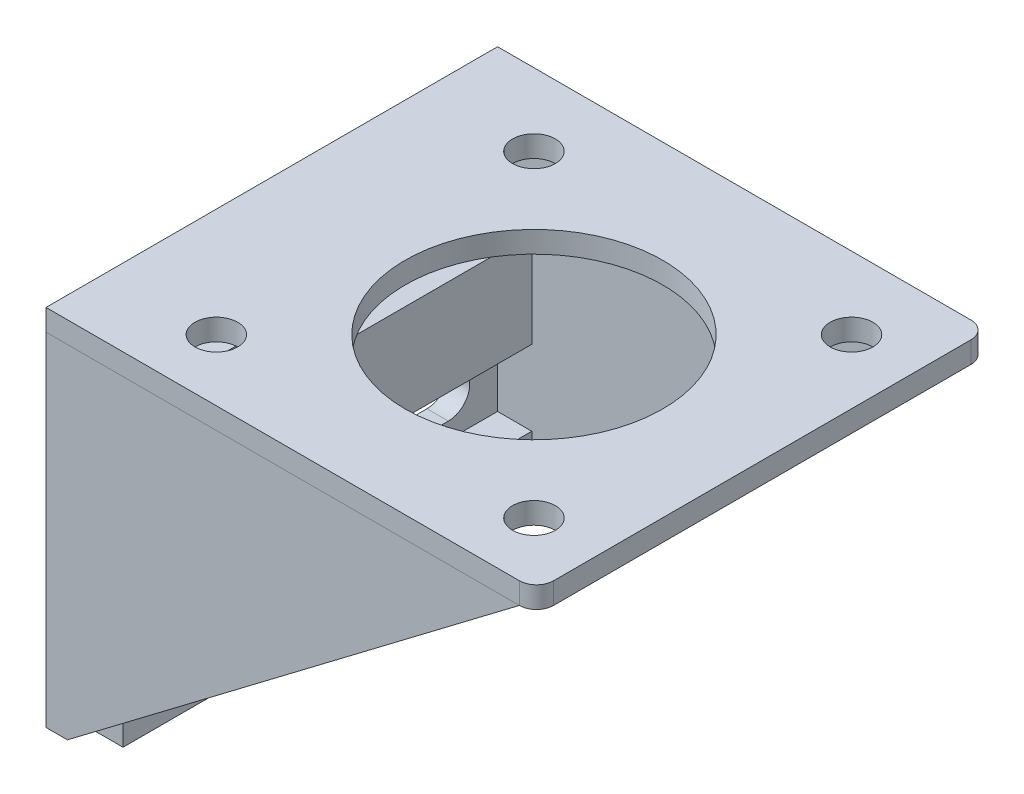
SolidWorks part; units mm, degrees
ref_plane "Front Plane" through (0, 0, 0) normal (0, 0, 1) x (1, 0, 0)
ref_plane "Top Plane" through (0, 0, 0) normal (0, 1, 0) x (1, 0, 0)
ref_plane "Right Plane" through (0, 0, 0) normal (1, 0, 0) x (0, 0, -1)
sketch "Sketch1" plane through (0, 0, 0) normal (0, 1, 0) x (1, 0, 0)
  line L0 (-26.2255, 26.2255) -> (-26.2255, -26.2255) construction
  line L1 (-26.2255, -26.2255) -> (26.2255, -26.2255) construction
  line L2 (26.2255, -26.2255) -> (26.2255, 26.2255) construction
  line L3 (26.2255, 26.2255) -> (-26.2255, 26.2255) construction
  line L4 (-26.2255, 26.2255) -> (26.2255, -26.2255) construction
  line L5 (-39.6875, 34.29) -> (33.0835, 34.29)
  line L6 (33.0835, 34.29) -> (33.0835, -32.7025)
  line L7 (33.0835, -32.7025) -> (-39.6875, -32.7025)
  line L8 (-39.6875, -32.7025) -> (-39.6875, 34.29)
  line L9 (-23.5585, 23.5585) -> (23.5585, 23.5585) construction
  line L10 (23.5585, 23.5585) -> (23.5585, -23.5585) construction
  line L11 (23.5585, -23.5585) -> (-23.5585, -23.5585) construction
  line L12 (-23.5585, -23.5585) -> (-23.5585, 23.5585) construction
  line L13 (26.7335, 27.5945) -> (26.7335, 19.7469) construction
  circle A0 centre (0, 0) radius 19.1135
  circle A1 centre (-23.5585, 23.5585) radius 2.667 construction
  circle A2 centre (23.5585, 23.5585) radius 2.667 construction
  circle A3 centre (-23.5585, -23.5585) radius 2.667 construction
  circle A4 centre (23.5585, -23.5585) radius 2.667 construction
  circle A5 centre (-23.5585, 23.5585) radius 3.175
  circle A6 centre (23.5585, 23.5585) radius 3.175
  circle A7 centre (23.5585, -23.5585) radius 3.175
  circle A8 centre (-23.5585, -23.5585) radius 3.175
  point P13 (0, 0)
  dimension "D1" = 38.227
  dimension "D2" = 5.334
  dimension "D8" = 6.35
  dimension "D3" = 52.451
  dimension "D5" = 34.29
  dimension "D6" = 32.7025
  dimension "D7" = 39.6875
  dimension "D4" = 6.35
extrude "Boss-Extrude1" add sketch "Sketch1" along normal blind 3.175
fillet "Fillet1" radius 2.54 2 edges at (33.0835, 1.5875, 32.7025) (33.0835, 1.5875, -34.29)
sketch "Sketch2" plane through (-39.6875, 0, 0) normal (-1, 0, 0) x (0, 0, 1)
  line L0 (-34.29, 0) -> (-34.29, -50.8)
  line L2 (32.7025, -50.8) -> (32.7025, 0)
  line L3 (-34.29, 0) -> (32.7025, 0)
  line L4 (32.7025, -50.8) -> (-34.29, -50.8)
  line L5 (-0.7938, 0) -> (-0.7938, -50.8) construction
  point P6 (-0.7938, -50.8)
  dimension "D1" = 50.8
extrude "Boss-Extrude2" add sketch "Sketch2" against normal blind 3.175
ref_plane "Plane1" through (-36.5125, 0, -34.29) normal (0, -1, 0) x (-1, 0, 0)
sketch "Sketch7" plane through (0, 0, 32.7025) normal (0, 0, 1) x (1, 0, 0)
  line L0 (-36.5125, -50.8) -> (30.5435, 0)
  line L1 (30.5435, 0) -> (-36.5125, 0)
  line L2 (-91.5125, 0) -> (18.4875, 0) construction
  line L3 (-36.5125, 0) -> (-36.5125, -50.8)
extrude "Boss-Extrude5" add sketch "Sketch7" against normal blind 3.175
sketch "Sketch8" plane through (0, 0, -34.29) normal (0, 0, -1) x (-1, 0, 0)
  line L0 (-30.5435, 0) -> (36.5125, 0)
  line L1 (36.5125, 0) -> (36.5125, -50.8)
  line L2 (36.5125, -50.8) -> (-30.5435, 0)
extrude "Boss-Extrude6" add sketch "Sketch8" against normal blind 3.175
sketch "Sketch9" plane through (-36.5125, 0, 0) normal (1, 0, 0) x (0, 0, -1)
  line L0 (-12.3825, -9.525) -> (23.8125, -9.525) construction
  line L1 (23.8125, -9.525) -> (23.8125, -34.925) construction
  line L2 (23.8125, -34.925) -> (-12.3825, -34.925) construction
  line L3 (-12.3825, -34.925) -> (-12.3825, -9.525) construction
  line L6 (-2.2225, -6.35) -> (-12.3825, -6.35)
  line L7 (-2.2225, -12.7) -> (-12.3825, -12.7)
  line L8 (-2.2225, -31.75) -> (-12.3825, -31.75)
  line L9 (-2.2225, -38.1) -> (-12.3825, -38.1)
  line L10 (23.8125, -38.1) -> (13.6525, -38.1)
  line L11 (23.8125, -31.75) -> (13.6525, -31.75)
  line L12 (23.8125, -6.35) -> (13.6525, -6.35)
  line L13 (23.8125, -12.7) -> (13.6525, -12.7)
  line L14 (-30.1625, 3.175) -> (31.75, 3.175) construction
  circle A0 centre (23.8125, -9.525) radius 3.175
  circle A1 centre (-12.3825, -9.525) radius 3.175
  circle A2 centre (23.8125, -34.925) radius 3.175
  circle A3 centre (-12.3825, -34.925) radius 3.175
  circle A4 centre (-2.2225, -9.525) radius 3.175
  circle A5 centre (13.6525, -9.525) radius 3.175
  circle A6 centre (13.6525, -34.925) radius 3.175
  circle A7 centre (-2.2225, -34.925) radius 3.175
  dimension "D1" = 6.35
  dimension "D2" = 12.3825
  dimension "D3" = 25.4
  dimension "D4" = 10.16
  dimension "D5" = 10.16
  dimension "D6" = 12.7
  dimension "D7" = 26.035
extrude "Cut-Extrude1" cut sketch "Sketch9" against normal blind 3.175 contours A4 L6 A1 L7 | A4 | A1 | A5 L13 A0 L12 | A5 | A0 | A2 | A6 L10 A2 L11 | A6 | A7 | A7 L8 A3 L9 | A3 region at (-36.5125, -9.525, 7.3025) region at (-36.5125, -9.525, 2.2225) region at (-36.5125, -9.525, 12.3825) region at (-36.5125, -34.925, 7.3025) region at (-36.5125, -34.925, 2.2225) region at (-36.5125, -34.925, 12.3825) region at (-36.5125, -34.925, -18.7325) region at (-36.5125, -34.925, -23.8125) region at (-36.5125, -34.925, -13.6525) region at (-36.5125, -9.525, -18.7325) region at (-36.5125, -9.525, -23.8125) region at (-36.5125, -9.525, -13.6525)
sketch "Sketch10" plane through (-36.5125, 0, 0) normal (1, 0, 0) x (0, 0, -1)
  line L0 (-29.5275, 0) -> (31.115, 0)
  line L1 (31.115, 0) -> (31.115, -3.937)
  line L2 (31.115, 0) -> (31.115, -50.8) construction
  line L3 (31.115, -3.937) -> (-29.5275, -3.937)
  line L4 (-29.5275, 0) -> (-29.5275, -50.8) construction
  line L5 (-29.5275, -3.937) -> (-29.5275, 0)
  line L6 (31.115, -15.113) -> (-29.5275, -15.113)
  line L7 (31.115, -50.8) -> (31.115, 0) construction
  line L8 (-29.5275, -50.8) -> (-29.5275, 0) construction
  line L9 (-29.5275, -15.113) -> (-29.5275, -29.337)
  line L10 (-29.5275, -29.337) -> (31.115, -29.337)
  line L11 (23.8125, -9.525) -> (23.8125, -3.937)
  line L12 (23.8125, -9.525) -> (23.8125, -15.113)
  line L13 (-29.5275, -40.513) -> (31.115, -40.513)
  line L14 (31.115, -40.513) -> (31.115, -50.8)
  line L15 (31.115, -50.8) -> (-29.5275, -50.8)
  line L16 (-29.5275, -50.8) -> (-29.5275, -40.513)
  line L17 (23.8125, -34.925) -> (23.8125, -29.337)
  line L18 (23.8125, -34.925) -> (23.8125, -40.513)
  line L19 (31.115, -29.337) -> (31.115, -15.113)
  line M29 (31.115, -50.8) -> (31.115, 0)
  line M30 (31.115, 0) -> (-29.5275, 0)
  line M31 (-29.5275, 0) -> (-29.5275, -50.8)
  line M32 (-29.5275, -50.8) -> (31.115, -50.8)
  dimension "D1" = 11.176
  dimension "D2" = 11.176
extrude "Boss-Extrude7" add sketch "Sketch10" along normal blind 5.08 contours L10 L6 M31 M29 | L3 M29 M30 M31 | L13 M31 M32 M29 region at (-36.5125, -1.9685, -0.7937) region at (-36.5125, -22.225, -0.7938) region at (-36.5125, -45.6565, -0.7938)
split "Split1" bodies to split 109 resulting bodies 110 111 split by face at (15.816, 0, -0.7938)
equation "\"D5@Sketch1\"=1.1+1/8+2/16"
equation "\"D6@Sketch1\"=1.1+1/8+1/16"
equation "\"D2@Sketch10\"=\"D1@Sketch10\""
